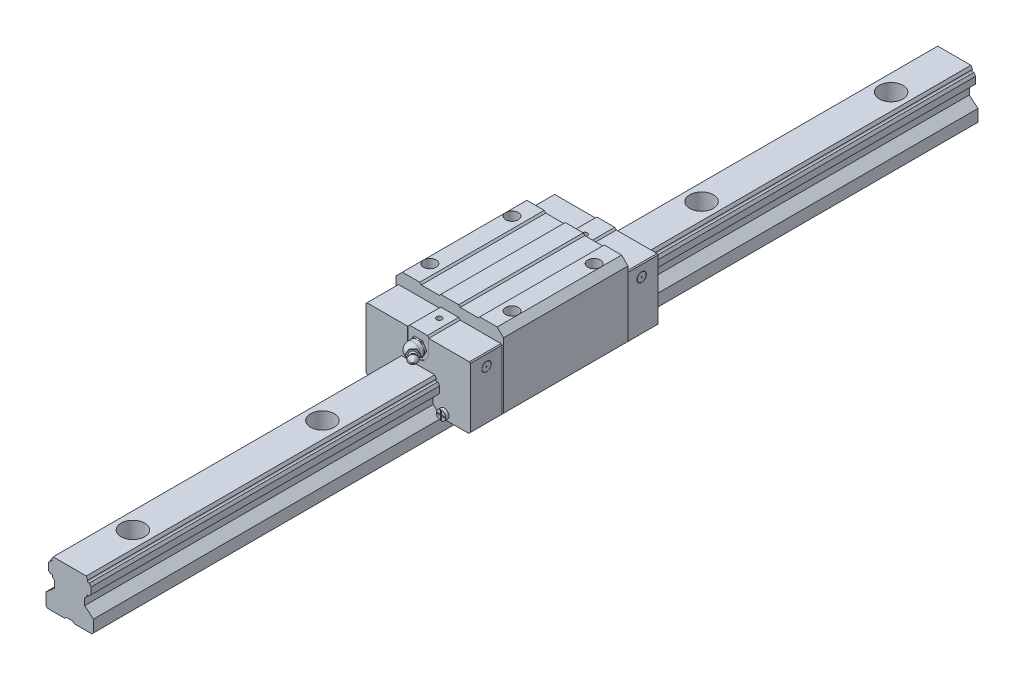
SolidWorks part; units mm, degrees
ref_plane "前视基准面" through (0, 0, 0) normal (0, 0, 1) x (1, 0, 0)
ref_plane "上视基准面" through (0, 0, 0) normal (0, 1, 0) x (1, 0, 0)
ref_plane "右视基准面" through (0, 0, 0) normal (1, 0, 0) x (0, 0, -1)
sketch "基准草图" plane through (0, 0, 0) normal (1, 0, 0) x (0, 0, -1)
  line L0 (0, 0) -> (60, 0) construction
  line L1 (0, 0) -> (0, 5)
  line L2 (60, 0) -> (80, 0) construction
  dimension "数量" = 5
  dimension "P" = 60
  dimension "E" = 20
sketch "草图1" plane through (0, 0, 0) normal (0, 0, 1) x (1, 0, 0)
  line L0 (0, 23.7) -> (0, 0) construction
  line L1 (-17, 21.7) -> (-17, 17.7)
  line L2 (17, 21.7) -> (17, 1)
  line L3 (-13, 23.7) -> (-13, 19.725) construction
  line L4 (-9.5, 23.7) -> (-9, 23.2)
  line L5 (-9, 23.2) -> (-3.3333, 23.2)
  line L6 (-3.3333, 23.2) -> (-2.8333, 23.7)
  line L7 (9.5, 23.7) -> (9, 23.2)
  line L8 (9, 23.2) -> (3.3333, 23.2)
  line L9 (3.3333, 23.2) -> (2.8333, 23.7)
  line L10 (-9.5, 23.7) -> (-15, 23.7)
  line L11 (15, 23.7) -> (9.5, 23.7)
  line L12 (-15, 23.7) -> (-17, 21.7)
  line L13 (2.8333, 23.7) -> (-2.8333, 23.7)
  line L14 (-16.2, 19.725) -> (16.2, 19.725)
  line L15 (-16.2, 19.725) -> (-16.5, 19.425)
  line L16 (-16.5, 19.425) -> (-16.5, 0.5)
  line L17 (-17, 17.7) -> (-16.5, 17.2) construction
  line L18 (-3.3333, 19.725) -> (-3.3333, 15.75)
  line L19 (3.3333, 19.725) -> (3.3333, 15.75)
  line L21 (-16, 0) -> (-7.5, 0)
  line L22 (-7.5, 0) -> (-4.75, 2.3075)
  line L23 (15, 23.7) -> (17, 21.7)
  line L24 (-4.75, 2.3075) -> (-4.75, 4.4182)
  line L25 (-4.75, 4.4182) -> (-5.4765, 5.0996)
  line L26 (-6.75, 6.294) -> (-6.75, 8.4047)
  line L27 (-6.75, 8.4047) -> (-6.2051, 9.2384)
  line L28 (-5.25, 10.7) -> (5.25, 10.7)
  line L29 (6.75, 8.4047) -> (6.2051, 9.2384)
  line L30 (6.75, 6.294) -> (6.75, 8.4047)
  line L31 (4.75, 4.4182) -> (5.4765, 5.0996)
  line L32 (4.75, 2.3075) -> (4.75, 4.4182)
  line L33 (7.5, 0) -> (4.75, 2.3075)
  line L34 (16, 0) -> (7.5, 0)
  line L35 (16.5, 19.425) -> (16.5, 0.5)
  line L36 (16.2, 19.725) -> (16.5, 19.425)
  line L37 (-7.5, 0) -> (-7.5, -3.8)
  line L38 (-7.5, -3.8) -> (-7, -4.3)
  line L39 (-7, -4.3) -> (-1.5, -4.3)
  line L40 (7.5, -3.8) -> (7, -4.3)
  line L41 (7.5, 0) -> (7.5, -3.8)
  line L42 (-1.5, -4.3) -> (-1, -3.8)
  line L43 (-1, -3.8) -> (1, -3.8)
  line L44 (1.5, -4.3) -> (1, -3.8)
  line L45 (1.5, -4.3) -> (7, -4.3)
  line L46 (-6.0235, 5.6126) -> (-6.75, 6.294)
  line L47 (-5.7949, 9.8662) -> (-5.25, 10.7)
  line L48 (5.7949, 9.8662) -> (5.25, 10.7)
  line L49 (6.0235, 5.6126) -> (6.75, 6.294)
  line L51 (8.2379, 3.1) -> (8.2379, 0.1) construction
  line L52 (6.7379, 1.6) -> (9.7379, 1.6) construction
  line L53 (8.0879, 2.9919) -> (8.0879, 1.75)
  line L54 (8.0879, 1.75) -> (6.846, 1.75)
  line L55 (8.3879, 1.75) -> (9.6299, 1.75)
  line L56 (8.3879, 2.9919) -> (8.3879, 1.75)
  line L57 (8.0879, 1.45) -> (6.846, 1.45)
  line L58 (8.3879, 1.45) -> (9.6299, 1.45)
  line L59 (8.3879, 0.2081) -> (8.3879, 1.45)
  line L60 (8.0879, 0.2081) -> (8.0879, 1.45)
  line L61 (-8.0879, 1.45) -> (-6.846, 1.45)
  line L62 (-8.0879, 0.2081) -> (-8.0879, 1.45)
  line L63 (-8.3879, 0.2081) -> (-8.3879, 1.45)
  line L64 (-8.3879, 1.45) -> (-9.6299, 1.45)
  line L65 (-8.3879, 1.75) -> (-9.6299, 1.75)
  line L66 (-8.0879, 1.75) -> (-6.846, 1.75)
  line L67 (-8.0879, 2.9919) -> (-8.0879, 1.75)
  line L68 (-8.3879, 2.9919) -> (-8.3879, 1.75)
  line L69 (-2.8333, 20.225) -> (2.8333, 20.225)
  line L70 (-3.3333, 19.725) -> (-2.8333, 20.225)
  line L71 (-16.75, 17.45) -> (-16.75, 0.75)
  line L72 (3.3333, 19.725) -> (2.8333, 20.225)
  line L73 (-16.75, 17.45) -> (-17, 17.7)
  line L74 (-16, 0) -> (-16.75, 0.75)
  line L75 (16, 0) -> (17, 1)
  arc A0 (-3.3333, 15.75) -> (3.3333, 15.75) centre (0, 15.75) ccw
  arc A1 (-6.2051, 9.2384) -> (-5.7949, 9.8662) centre (-6, 9.5523) ccw
  arc A2 (-5.4765, 5.0996) -> (-6.0235, 5.6126) centre (-5.75, 5.3561) ccw
  arc A3 (5.4765, 5.0996) -> (6.0235, 5.6126) centre (5.75, 5.3561) cw
  arc A4 (6.2051, 9.2384) -> (5.7949, 9.8662) centre (6, 9.5523) cw
  circle A5 centre (8.2379, 1.6) radius 1.5
  circle A6 centre (-8.2379, 1.6) radius 1.5
  circle A7 centre (8.2379, 1.6) radius 1.4
  circle A8 centre (-8.2379, 1.6) radius 1.4
  point P4 (-13, 23.7)
  point P6 (13, 23.7)
  point P11 (-9.5, 23.7)
  point P12 (-2.8333, 23.7)
  point P13 (9.5, 23.7)
  point P14 (2.8333, 23.7)
  point P55 (-7.5, 0)
  point P60 (0, 12.4167)
  dimension "D18" = 0.75
  dimension "D19" = 0.75
  dimension "D20" = 3
  dimension "D21" = 1.7
  dimension "D24" = 0.1
  dimension "D25" = 1.6
  dimension "D1" = 2
  dimension "D2" = 45
  dimension "W" = 34
  dimension "D3" = 45
  dimension "B1" = 4
  dimension "B" = 26
  dimension "T" = 6
  dimension "H" = 28
  dimension "D4" = 45
  dimension "D5" = 0.5
  dimension "D6" = 6.6667
  dimension "D7" = 45
  dimension "D8" = 0.5
  dimension "D9" = 0.5
  dimension "H2" = 7.95
  dimension "D10" = 3.975
  dimension "D11" = 45
  dimension "Wr" = 15
  dimension "D12" = 2
  dimension "N" = 9.5
  dimension "D13" = 45
  dimension "D14" = 9.5
  dimension "H1" = 4.3
  dimension "D15" = 0.3
  dimension "D16" = 10.5
  dimension "D17" = 0.3
  dimension "D22" = 0.3
  dimension "D23" = 0.3
  dimension "D26" = 0.5
  dimension "D27" = 45
  dimension "Hr" = 15
  dimension "D28" = 1.5
  dimension "D29" = 100
  dimension "D30" = 40
  dimension "D31" = 1
  dimension "D32" = 1
  dimension "D33" = 45
extrude "凸台-拉伸11" add sketch "草图1" along normal mid plane 59.4 contours A4 L29 L30 L49 A3 L31 L32 L33 L34 L35 L36 L14 L19 A0 L18 L15 L16 L21 L22 L24 L25 A2 L46 L26 L27 A1 L47 L28 L48 A5 A6 | L18 A0 L19 L69 | L14 L72 L69 L70 region at (-16.1155, 9.9625, 0) region at (0, 19.9682, 0) region at (0, 16.3865, 0)
extrude "凸台-拉伸12" add sketch "草图1<12>" along normal mid plane 61.4 contours A5 | A6
sketch "草图1<12>" plane through (0, 0, 0) normal (0, 0, 1) x (1, 0, 0) same geometry as "草图1"
extrude "凸台-拉伸13" add sketch "草图1<13>" along normal mid plane 39.4 contours L2 L23 L11 L7 L8 L9 L13 L6 L5 L4 L10 L12 L1 L17 L16 L15 L14 L36 L35 region at (0.515, 20.4225, 0)
sketch "草图1<13>" plane through (0, 0, 0) normal (0, 0, 1) x (1, 0, 0) same geometry as "草图1"
extrude "凸台-拉伸14" add sketch "草图1<14>" along normal mid plane 280 contours L29 A4 L48 L28 L47 A1 L27 L26 L46 A2 L25 L24 L22 L37 L38 L39 L42 L43 L44 L45 L40 L41 L33 L32 L31 A3 L49 L30 region at (0, 2.9055, 0)
sketch "草图1<14>" plane through (0, 0, 0) normal (0, 0, 1) x (1, 0, 0) same geometry as "草图1"
sketch "草图4" plane through (0, 0, 30.7) normal (0, 0, 1) x (1, 0, 0)
  line L0 (8.0879, 1.75) -> (6.846, 1.75) construction
  line L1 (8.0879, 2.9919) -> (8.0879, 1.75) construction
  line L2 (8.3879, 2.9919) -> (8.3879, 1.75) construction
  line L3 (8.3879, 1.75) -> (9.6299, 1.75) construction
  line L4 (8.3879, 1.45) -> (9.6299, 1.45) construction
  line L5 (8.3879, 0.2081) -> (8.3879, 1.45) construction
  line L6 (8.0879, 0.2081) -> (8.0879, 1.45) construction
  line L7 (8.0879, 1.45) -> (6.846, 1.45) construction
  line L8 (8.0879, 1.75) -> (6.846, 1.75)
  line L9 (8.0879, 2.9919) -> (8.0879, 1.75)
  line L10 (8.3879, 2.9919) -> (8.3879, 1.75)
  line L11 (8.3879, 1.75) -> (9.6299, 1.75)
  line L12 (8.3879, 1.45) -> (9.6299, 1.45)
  line L13 (8.3879, 0.2081) -> (8.3879, 1.45)
  line L14 (8.0879, 0.2081) -> (8.0879, 1.45)
  line L15 (8.0879, 1.45) -> (6.846, 1.45)
  line L16 (-8.0879, 2.9919) -> (-8.0879, 1.75) construction
  line L17 (-8.3879, 2.9919) -> (-8.3879, 1.75) construction
  line L18 (-8.3879, 1.75) -> (-9.6299, 1.75) construction
  line L19 (-8.3879, 1.45) -> (-9.6299, 1.45) construction
  line L20 (-8.3879, 0.2081) -> (-8.3879, 1.45) construction
  line L21 (-8.0879, 0.2081) -> (-8.0879, 1.45) construction
  line L22 (-8.0879, 1.45) -> (-6.846, 1.45) construction
  line L23 (-8.0879, 1.75) -> (-6.846, 1.75) construction
  line L24 (-8.0879, 2.9919) -> (-8.0879, 1.75)
  line L25 (-8.3879, 2.9919) -> (-8.3879, 1.75)
  line L26 (-8.3879, 1.75) -> (-9.6299, 1.75)
  line L27 (-8.3879, 1.45) -> (-9.6299, 1.45)
  line L28 (-8.3879, 0.2081) -> (-8.3879, 1.45)
  line L29 (-8.0879, 0.2081) -> (-8.0879, 1.45)
  line L30 (-8.0879, 1.45) -> (-6.846, 1.45)
  line L31 (-8.0879, 1.75) -> (-6.846, 1.75)
  circle A0 centre (8.2379, 1.6) radius 1.4 construction
  arc A1 (6.846, 1.75) -> (6.846, 1.45) centre (8.2379, 1.6) ccw
  arc A2 (8.0879, 0.2081) -> (8.3879, 0.2081) centre (8.2379, 1.6) ccw
  arc A3 (8.3879, 2.9919) -> (8.0879, 2.9919) centre (8.2379, 1.6) ccw
  arc A4 (9.6299, 1.45) -> (9.6299, 1.75) centre (8.2379, 1.6) ccw
  circle A5 centre (-8.2379, 1.6) radius 1.4 construction
  arc A6 (-9.6299, 1.75) -> (-9.6299, 1.45) centre (-8.2379, 1.6) ccw
  arc A7 (-8.0879, 2.9919) -> (-8.3879, 2.9919) centre (-8.2379, 1.6) ccw
  arc A8 (-6.846, 1.45) -> (-6.846, 1.75) centre (-8.2379, 1.6) ccw
  arc A9 (-8.3879, 0.2081) -> (-8.0879, 0.2081) centre (-8.2379, 1.6) ccw
extrude "切除-拉伸1" cut sketch "草图4" against normal blind 0.5
mirror "镜向1" about plane through (0, 0, 0) normal (0, 0, 1) of "切除-拉伸1"
sketch "草图6" plane through (0, 23.7, 0) normal (0, 1, 0) x (1, 0, 0)
  line L0 (-17, 0) -> (17, 0) construction
  line L5 (0, 29.7) -> (0, -29.7) construction
  line L8 (-5.25, 29.7) -> (5.25, 29.7) construction
  line L9 (-2.8333, -29.7) -> (2.8333, -29.7) construction
  line L13 (-17, -19.7) -> (-17, 19.7) construction
  line L14 (17, -19.7) -> (17, 19.7) construction
  circle A0 centre (-13, 13) radius 2
  circle A1 centre (-13, -13) radius 2
  circle A2 centre (13, -13) radius 2
  circle A3 centre (13, 13) radius 2
  dimension "M" = 4
  dimension "C" = 26
extrude "切除-拉伸3" cut sketch "草图6" against normal blind 5
cosmetic thread "装饰螺纹线1" parameters "D1"=8.975, "D2"=4.1
cosmetic thread "装饰螺纹线2" parameters "D1"=5, "D2"=4.1
cosmetic thread "装饰螺纹线3" parameters "D1"=5, "D2"=4.1
cosmetic thread "装饰螺纹线4" parameters "D1"=8.975, "D2"=4.1
sketch "草图7" plane through (0, 20.225, 0) normal (0, 1, 0) x (1, 0, 0)
  line L0 (0, 29.7) -> (0, -29.7) construction
  line L1 (-5.25, 29.7) -> (5.25, 29.7) construction
  line L2 (-2.8333, -29.7) -> (2.8333, -29.7) construction
  line L3 (-17, 0) -> (17, 0) construction
  line L4 (-17, -19.7) -> (-17, 19.7) construction
  line L5 (17, -19.7) -> (17, 19.7) construction
  circle A0 centre (0, 23) radius 0.8368
  circle A1 centre (-13, 13) radius 2 construction
  circle A2 centre (0, -23) radius 0.8368
  dimension "D1" = 1.6736
  dimension "K1" = 10
extrude "切除-拉伸4" cut sketch "草图7" against normal blind 8
sketch "草图8" plane through (0, 0, 29.7) normal (0, 0, 1) x (1, 0, 0)
  line L3 (3.3333, 19.725) -> (3.3333, 15.75) construction
  line L4 (-3.3333, 19.725) -> (-3.3333, 15.75) construction
  line L5 (-16.2, 19.725) -> (16.2, 19.725) construction
  line L6 (-3.3333, 19.725) -> (-2.8333, 20.225) construction
  line L7 (-2.8333, 20.225) -> (2.8333, 20.225) construction
  line L8 (3.3333, 19.725) -> (2.8333, 20.225) construction
  line L9 (3.3333, 19.725) -> (3.3333, 15.75)
  line L10 (-3.3333, 19.725) -> (-3.3333, 15.75)
  line L11 (-16.2, 19.725) -> (-3.3333, 19.725)
  line L12 (-3.3333, 19.725) -> (-2.8333, 20.225)
  line L13 (-2.8333, 20.225) -> (2.8333, 20.225)
  line L14 (3.3333, 19.725) -> (2.8333, 20.225)
  line L15 (3.3333, 19.725) -> (16.2, 19.725)
  arc A0 (-3.3333, 15.75) -> (3.3333, 15.75) centre (0, 15.75) ccw construction
  arc A1 (-3.3333, 15.75) -> (3.3333, 15.75) centre (0, 15.75) ccw
  line M2 (2.8333, 20.225) -> (-2.8333, 20.225)
  line M41 (3.3333, 19.725) -> (2.8333, 20.225)
  line M42 (-2.8333, 20.225) -> (-3.3333, 19.725)
extrude "切除-拉伸6" cut sketch "草图8" against normal blind 0.1 contours L10 A1 L9 M41 M2 M42 region at (0, 16.6213, 29.7)
ref_plane "基准面1" through (0, 15.75, 0) normal (0, 1, 0) x (-1, 0, 0)
sketch "草图9" plane through (0, 15.75, 0) normal (0, 1, 0) x (-1, 0, 0)
  line L0 (0, 29.6) -> (0, 33.6)
  line L1 (-0.6758, 33.5815) -> (-0.393, 33.8643) construction
  line L2 (-2.25, 29.6) -> (-2.25, 31.35)
  line L3 (-2.25, 29.6) -> (0, 29.6)
  line L4 (-3.3333, 29.7) -> (-16.2, 29.7) construction
  line L5 (5.25, 29.7) -> (-5.25, 29.7) construction
  line L7 (-2.8333, 29.6) -> (2.8333, 29.6) construction
  line L8 (0, 31.35) -> (-1.291, 32.641) construction
  line L9 (-1.291, 32.641) -> (-0.2303, 33.7017) construction
  line L10 (-0.2303, 33.7017) -> (-0.393, 33.8643) construction
  line L12 (-0.6758, 33.5815) -> (-1.1758, 33.5815) construction
  line L13 (-1.1758, 33.5815) -> (-1.6921, 35) construction
  line L14 (-1.291, 32.641) -> (-3.5524, 34.9024) construction
  line L15 (-1.6921, 35) -> (-3.4548, 35) construction
  line L16 (-3.4548, 35) -> (-3.5524, 34.9024) construction
  arc A0 (0, 33.6) -> (-2.25, 31.35) centre (0, 31.35) ccw
  point P7 (2.25, 31.35)
  point P8 (-1.591, 32.941)
  point P20 (0, 35)
  dimension "D1" = 4.5
  dimension "D2" = 4
  dimension "D3" = 45
  dimension "D4" = 5.3
  dimension "D5" = 0.3
  dimension "D6" = 0.5
  dimension "D7" = 110
  dimension "D8" = 0.138
  dimension "D9" = 0.4
  dimension "D10" = 0.2301
  dimension "D11" = 1.5
  dimension "G" = 5.3
revolve "旋转1" add sketch "草图9" angle 360 about L0
sketch "草图10" plane through (0, 15.75, 0) normal (0, 1, 0) x (-1, 0, 0)
  line L0 (-1.1758, 33.5815) -> (-1.6921, 35) construction
  line L1 (-1.6921, 35) -> (-3.4548, 35) construction
  line L2 (-3.4548, 35) -> (-3.5524, 34.9024) construction
  line L3 (-1.291, 32.641) -> (-3.5524, 34.9024) construction
  line L4 (-1.291, 32.641) -> (-0.2303, 33.7017) construction
  line L5 (-0.2303, 33.7017) -> (-0.393, 33.8643) construction
  line L6 (-0.6758, 33.5815) -> (-0.393, 33.8643) construction
  line L7 (-0.6758, 33.5815) -> (-1.1758, 33.5815) construction
  line L8 (-1.1758, 33.5815) -> (-1.6921, 35)
  line L9 (-1.6921, 35) -> (-3.4548, 35)
  line L10 (-3.4548, 35) -> (-3.5524, 34.9024)
  line L11 (-1.291, 32.641) -> (-3.5524, 34.9024)
  line L12 (-1.291, 32.641) -> (-0.2303, 33.7017)
  line L13 (-0.2303, 33.7017) -> (-0.393, 33.8643)
  line L14 (-0.6758, 33.5815) -> (-0.393, 33.8643)
  line L15 (-0.6758, 33.5815) -> (-1.1758, 33.5815)
revolve "旋转2" add sketch "草图10" angle 360 about L14
sketch "草图11" plane through (0, 10.7, 0) normal (0, 1, 0) x (1, 0, 0)
  line L1 (-5.25, -140) -> (5.25, -140) construction
  line L2 (0, -140) -> (0, 140) construction
  line L3 (-5.25, 140) -> (5.25, 140) construction
  circle A0 centre (0, -120) radius 3.75
  circle A1 centre (0, -120) radius 2.25
  dimension "D" = 7.5
  dimension "(d)" = 4.5
  dimension "E" = 20
extrude "切除-拉伸7" cut sketch "草图11" against normal blind 5.3
sketch "草图12" plane through (0, 10.7, 0) normal (0, 1, 0) x (1, 0, 0)
  circle A2 centre (0, -120) radius 2.25 construction
  circle A3 centre (0, -120) radius 2.25
extrude "切除-拉伸8" cut sketch "草图12" against normal blind 15
pattern_linear "阵列(线性)1" count 5 spacing 60 along (0, 0, -1) of "切除-拉伸7", "切除-拉伸8"
sketch "草图13" plane through (16.5, 0, 0) normal (1, 0, 0) x (0, 0, -1)
  line L0 (-19.7, 21.7) -> (-19.7, 1) construction
  line L1 (-19.7, 23.7) -> (-13, 23.7) construction
  line L2 (0, 23.7) -> (0, 0) construction
  circle A0 centre (-24.55, 16) radius 1.5
  circle A1 centre (24.55, 16) radius 1.5
  circle A2 centre (-24.55, 16) radius 1.4
  circle A3 centre (-24.55, 16) radius 0.2
  circle A4 centre (24.55, 16) radius 0.2
  circle A5 centre (24.55, 16) radius 1.4
  dimension "D1" = 3
  dimension "D2" = 2.8
  dimension "D3" = 0.4
  dimension "K2" = 4.85
  dimension "H3" = 7.7
extrude "切除-拉伸9" cut sketch "草图13" against normal blind 5 contours A0 A2 | A3 | A1 A5 | A4 region at (16.5, 16, 26.0076) region at (16.5, 16, -23.0924) region at (16.5, 16, 24.55) region at (16.5, 16, -24.55)
combine bodies "组合1" operation type add bodies to combine 116 120
sketch "草图14" plane through (0, 0, 29.6) normal (0, 0, 1) x (1, 0, 0)
  line L1 (2.5981, 15.75) -> (1.299, 18)
  line L2 (1.299, 18) -> (-1.299, 18)
  line L3 (-1.299, 18) -> (-2.5981, 15.75)
  line L4 (-2.5981, 15.75) -> (-1.299, 13.5)
  line L5 (-1.299, 13.5) -> (1.299, 13.5)
  line L6 (1.299, 13.5) -> (2.5981, 15.75)
  circle A0 centre (0, 15.75) radius 2.25 construction
  circle A1 centre (0, 15.75) radius 2.25 construction
  circle A2 centre (0, 15.75) radius 2.25 construction
extrude "凸台-拉伸16" add sketch "草图14" along normal blind 0.5
sketch "草图15" plane through (17.1287, 0, 17.1287) normal (0.7071, 0, 0.7071) x (0.7071, 0, -0.7071)
  line L1 (-20.4357, 15.75) -> (-21.3018, 17.25)
  line L2 (-21.3018, 17.25) -> (-23.0338, 17.25)
  line L3 (-23.0338, 17.25) -> (-23.8998, 15.75)
  line L4 (-23.8998, 15.75) -> (-23.0338, 14.25)
  line L5 (-23.0338, 14.25) -> (-21.3018, 14.25)
  line L6 (-21.3018, 14.25) -> (-20.4357, 15.75)
  circle A0 centre (-22.1678, 15.75) radius 1.5 construction
  circle A1 centre (-22.1678, 15.75) radius 1.5 construction
  circle A2 centre (-22.1678, 15.75) radius 1.5 construction
extrude "凸台-拉伸17" add sketch "草图15" against normal up to surface (0.2301 mm away) up to face at (0.2303, 15.75, 33.7017)
